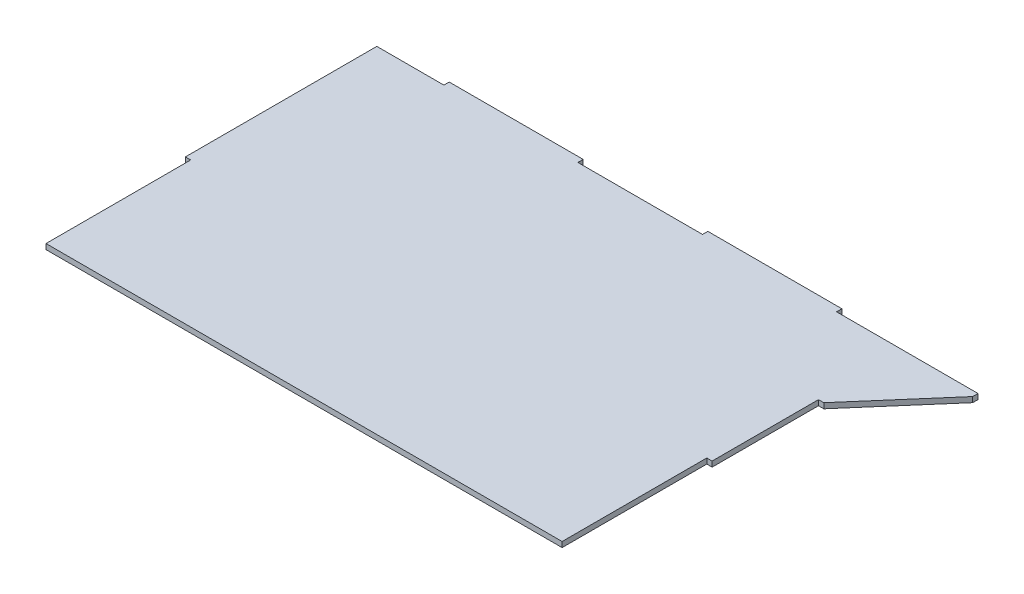
SolidWorks part; units mm, degrees
material "6061-T6 (SS)"
ref_plane "X-Y Datum" through (0, 0, 0) normal (0, 0, 1) x (1, 0, 0)
ref_plane "X-Z Datum" through (0, 0, 0) normal (0, 1, 0) x (1, 0, 0)
ref_plane "Y-Z Datum" through (0, 0, 0) normal (1, 0, 0) x (0, 0, -1)
sketch "Sketch1" plane through (0, 0, 0) normal (0, 0, 1) x (1, 0, 0)
  line L1 (-157.2306, -1.5875) -> (157.2306, -1.5875)
  line L2 (-157.2306, -1.5875) -> (-157.2306, 1.5875)
  line L3 (-157.2306, 1.5875) -> (157.2306, 1.5875)
  line L4 (157.2306, -1.5875) -> (157.2306, 1.5875)
  line L5 (-157.2306, -1.5875) -> (157.2306, 1.5875) construction
  line L6 (-157.2306, 1.5875) -> (157.2306, -1.5875) construction
  point P0 (0, 0)
  dimension "D1" = 314.4612
  dimension "D2" = 3.175
extrude "Boss-Extrude1" add sketch "Sketch1" along normal blind 200.6618
sketch "Sketch3" plane through (0, 0, 0) normal (0, 0, -1) x (-1, 0, 0)
  line L0 (-157.2306, 0) -> (-77.2306, 0) construction
  line L1 (-157.2306, -1.5875) -> (-157.2306, 1.5875) construction
  line L2 (-157.2306, 1.5875) -> (157.2306, 1.5875) construction
  line L3 (-117.2306, -1.5875) -> (-37.2306, -1.5875)
  line L4 (-117.2306, -1.5875) -> (-117.2306, 1.5875)
  line L5 (-117.2306, 1.5875) -> (-37.2306, 1.5875)
  line L6 (-37.2306, -1.5875) -> (-37.2306, 1.5875)
  line L7 (-117.2306, -1.5875) -> (-37.2306, 1.5875) construction
  line L8 (-117.2306, 1.5875) -> (-37.2306, -1.5875) construction
  line L14 (-157.2306, 1.5875) -> (-117.2306, 1.5875)
  line L15 (-157.2306, 1.5875) -> (-157.2306, -1.5875)
  line L16 (-157.2306, -1.5875) -> (-117.2306, -1.5875)
  line L17 (-117.2306, 1.5875) -> (-117.2306, -1.5875)
  line L19 (-37.2306, 1.5875) -> (-37.2306, -1.5875)
  line M3 (-157.2306, -1.5875) -> (157.2306, -1.5875)
  line M5 (157.2306, 1.5875) -> (-157.2306, 1.5875)
  dimension "D1" = 40
  dimension "D2" = 80
sketch "Sketch5" plane through (0, 1.5875, 0) normal (0, 1, 0) x (1, 0, 0)
  line L1 (-157.2306, -200.6618) -> (-154.0556, -200.6618)
  line L3 (-157.2306, -200.6618) -> (-157.2306, -114.3018)
  line L5 (-157.2306, -114.3018) -> (-154.0556, -114.3018)
  line L6 (-154.0556, -200.6618) -> (-154.0556, -114.3018)
  line M11 (-157.2306, 0) -> (-157.2306, -200.6618)
  line M12 (-157.2306, -200.6618) -> (157.2306, -200.6618)
  dimension "D1" = 86.36
  dimension "D2" = 3.175
extrude "Cut-Extrude2" cut sketch "Sketch5" against normal blind 3.175 and the other way through all contours M12 M11 region at (-155.6431, 1.5875, 157.4818)
mirror "Mirror1" about plane through (0, 0, 0) normal (1, 0, 0) of "Cut-Extrude2"
sketch "Sketch6" plane through (0, 1.5875, 0) normal (0, 1, 0) x (1, 0, 0)
  line L6 (-157.2306, -180.3418) -> (-81.0306, -180.3418)
  line L7 (-157.2306, -180.3418) -> (-157.2306, -200.6618)
  line L8 (-157.2306, -200.6618) -> (-81.0306, -200.6618)
  line L9 (-81.0306, -180.3418) -> (-81.0306, -200.6618)
  line L10 (154.0556, -200.6618) -> (-154.0556, -200.6618) construction
  line L11 (-157.2306, -114.3018) -> (-157.2306, 0) construction
  line L13 (154.0556, -200.6618) -> (-81.0306, -200.6618)
  line L14 (154.0556, -200.6618) -> (154.0556, -180.3418)
  line L15 (154.0556, -180.3418) -> (-81.0306, -180.3418)
  line L16 (-81.0306, -200.6618) -> (-81.0306, -180.3418)
  line M18 (-154.0556, -114.3018) -> (-154.0556, -200.6618)
  line M19 (-154.0556, -200.6618) -> (154.0556, -200.6618)
  dimension "D1" = 76.2
  dimension "D2" = 20.32
extrude "Cut-Extrude4" [suppressed] cut sketch "Sketch6" against normal through all contours L9 L6 M18 M19
sketch "Sketch7" [suppressed] plane through (0, 1.5875, 0) normal (0, 1, 0) x (1, 0, 0)
  line L1 (-81.2823, -215.455) -> (155.1963, -215.455)
  line L2 (-81.2823, -215.455) -> (-81.2823, -235.775)
  line L3 (-81.2823, -235.775) -> (155.1963, -235.775)
  line L4 (155.1963, -215.455) -> (155.1963, -235.775)
extrude "Cut-Extrude5" [suppressed] cut sketch "Sketch7" against normal through all
sketch "Sketch8" [suppressed] plane through (0, 1.5875, 0) normal (0, 1, 0) x (1, 0, 0)
  line L0 (155.1963, -235.775) -> (-155.1963, -235.775) construction
  line L1 (157.4823, -215.455) -> (81.2823, -215.455)
  line L2 (157.4823, -215.455) -> (157.4823, -235.775)
  line L3 (157.4823, -235.775) -> (81.2823, -235.775)
  line L4 (81.2823, -215.455) -> (81.2823, -235.775)
  line L5 (157.4823, -117.411) -> (157.4823, -3.175) construction
  dimension "D1" = 20.32
  dimension "D2" = 76.2
extrude "Cut-Extrude6" [suppressed] cut sketch "Sketch8" against normal through all
sketch "Sketch9" [suppressed] plane through (0, 0, 215.455) normal (0, 0, 1) x (1, 0, 0)
  line L4 (155.1963, 1.5875) -> (-155.1963, 1.5875)
  line L5 (-155.1963, 1.5875) -> (-155.1963, -1.5875)
  line L6 (-155.1963, -1.5875) -> (155.1963, -1.5875)
  line L7 (155.1963, -1.5875) -> (155.1963, 1.5875)
  line L8 (155.1963, 1.5875) -> (-155.1963, 1.5875)
  line L9 (-155.1963, 1.5875) -> (-155.1963, -1.5875)
  line L10 (-155.1963, -1.5875) -> (155.1963, -1.5875)
  line L11 (155.1963, -1.5875) -> (155.1963, 1.5875)
  dimension "D1" = 0
extrude "Cut-Extrude7" [suppressed] cut sketch "Sketch9" against normal blind 11.68
extrude "Boss-Extrude2" add sketch "Sketch3" along normal blind 3.175 contours L6 L4 M3 M5 region at (77.2306, 0, 0)
pattern_linear "LPattern2" count 2 spacing 154.43 along (-1, 0, 0) of "Boss-Extrude2"
sketch "Sketch10" plane through (0, -1.5875, 0) normal (0, -1, 0) x (1, 0, 0)
  line L2 (201.6654, 0) -> (201.6654, 3.175)
  line L8 (157.2306, 0) -> (201.6654, 0)
  line L10 (157.2306, 114.3018) -> (157.2306, 0) construction
  line L11 (157.2306, 50.8) -> (157.2306, 0)
  line L12 (157.2306, 50.8) -> (160.4056, 50.8)
  line L13 (160.4056, 50.8) -> (201.6654, 3.175)
  dimension "D1" = 50.8
  dimension "D2" = 44.4348
  dimension "D3" = 3.175
  dimension "D4" = 3.175
extrude "Boss-Extrude3" add sketch "Sketch10" against normal blind 3.175
sketch "Sketch11" [suppressed] plane through (0, 0, 0) normal (0, 0, -1) x (-1, 0, 0)
  line L1 (37.2652, -1.5875) -> (117.2652, -1.5875)
  line L2 (37.2652, -1.5875) -> (37.2652, 1.5875)
  line L3 (37.2652, 1.5875) -> (117.2652, 1.5875)
  line L4 (117.2652, -1.5875) -> (117.2652, 1.5875)
  line L5 (-117.1668, -1.5875) -> (-37.1668, -1.5875)
  line L6 (-117.1668, -1.5875) -> (-117.1668, 1.5875)
  line L7 (-117.1668, 1.5875) -> (-37.1668, 1.5875)
  line L8 (-37.1668, -1.5875) -> (-37.1668, 1.5875)
extrude "Boss-Extrude4" [suppressed] add sketch "Sketch11" along normal blind 3.175
